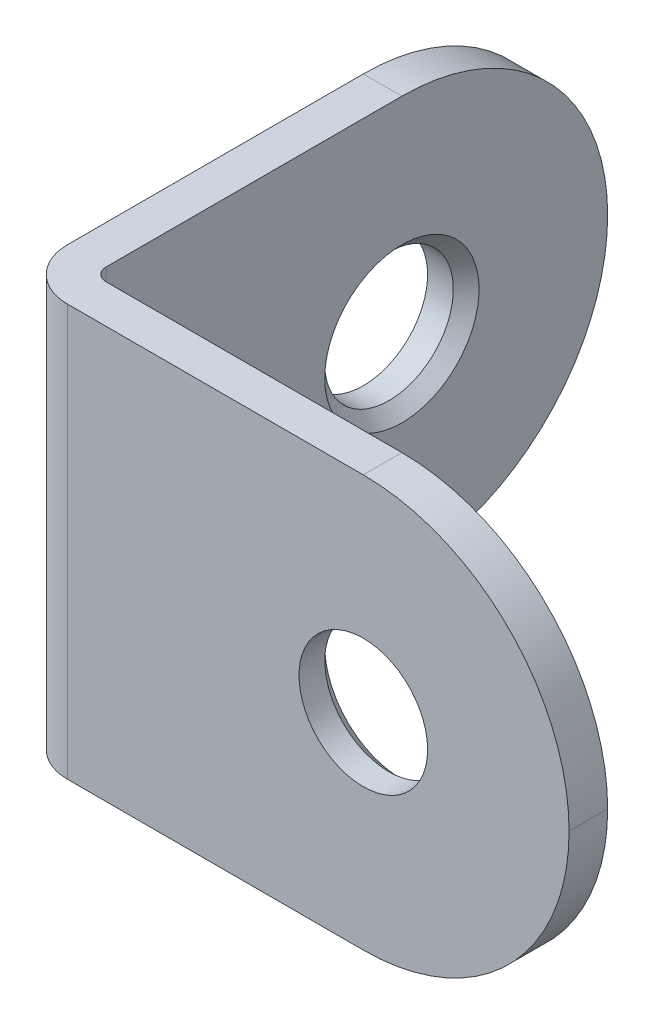
SolidWorks part; units mm, degrees
ref_plane "Спереди" through (0, 0, 0) normal (0, 0, 1) x (1, 0, 0)
ref_plane "Сверху" through (0, 0, 0) normal (0, 1, 0) x (1, 0, 0)
ref_plane "Справа" through (0, 0, 0) normal (1, 0, 0) x (0, 0, -1)
other "Configuration Table"
sketch "Эскиз1" plane through (0, 0, 0) normal (0, 1, 0) x (1, 0, 0)
  line L0 (0, 20) -> (0, 0)
  line L1 (0, 0) -> (20, 0)
  line L2 (-1.5, 20) -> (-1.5, -1.5)
  line L3 (-1.5, -1.5) -> (20, -1.5)
  line L4 (-1.5, 20) -> (0, 20)
  line L5 (20, 0) -> (20, -1.5)
  dimension "D1" = 20
  dimension "D2" = 20
  dimension "D3" = 1.5
extrude "Бобышка-Вытянуть1" add sketch "Эскиз1" along normal blind 16
fillet "Скругление1" radius 8 4 edges at (-0.75, 0, -20) (-0.75, 16, -20) (20, 0, 0.75) (20, 16, 0.75)
sketch "Эскиз2" plane through (0, 0, 1.5) normal (0, 0, 1) x (1, 0, 0)
  circle A0 centre (12, 8) radius 2.5
  dimension "D1" = 5
extrude "Вырез-Вытянуть1" cut sketch "Эскиз2" against normal blind 16
sketch "Эскиз3" plane through (-1.5, 0, 0) normal (-1, 0, 0) x (0, 0, 1)
  circle A0 centre (-12, 8) radius 2.5
  dimension "D1" = 5
extrude "Вырез-Вытянуть2" cut sketch "Эскиз3" against normal blind 16
fillet "Скругление3" radius 2 1 edges at (-1.5, 8, 1.5)
fillet "Скругление4" radius 0.5 1 edges at (0, 8, 0)
chamfer "Фаска1" distance 0.5 angle 45 2 edges at (0, 8, -9.5) (14.5, 8, 0)
